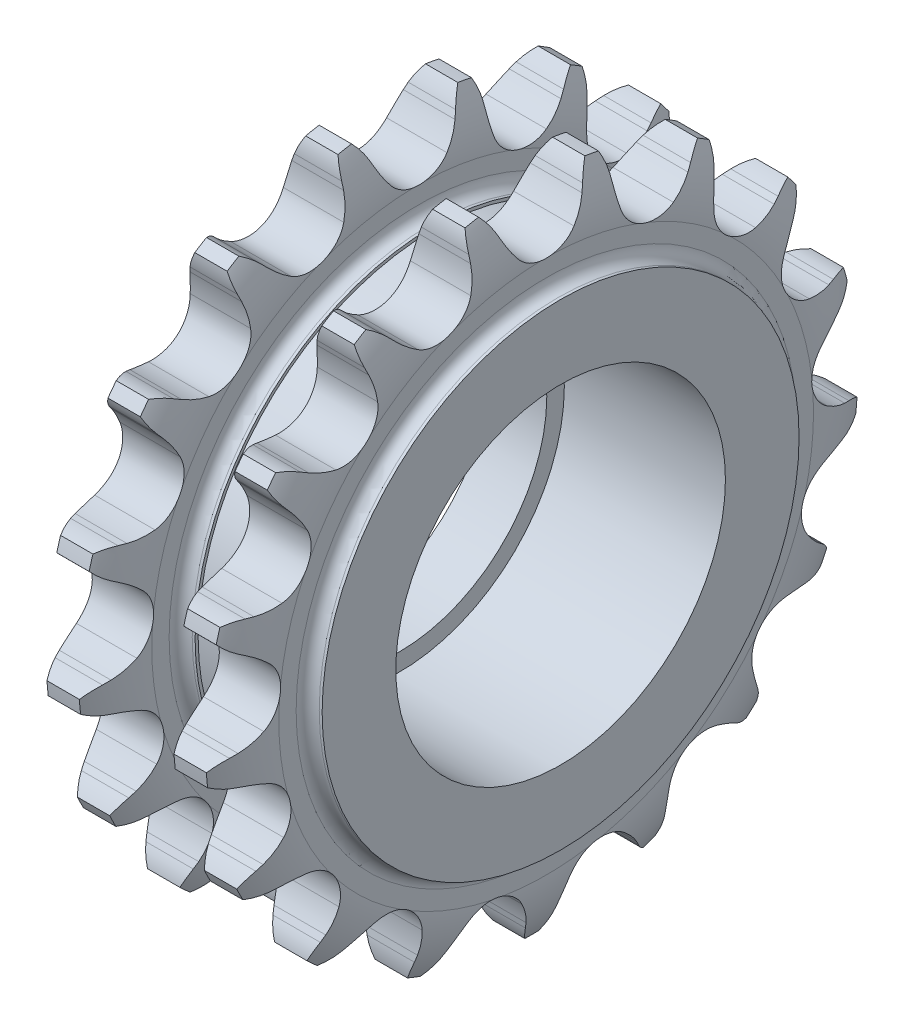
SolidWorks part; units mm, degrees
material "AISI 1020"
ref_plane "Front" through (0, 0, 0) normal (0, 0, 1) x (1, 0, 0)
ref_plane "Top" through (0, 0, 0) normal (0, 1, 0) x (1, 0, 0)
ref_plane "Right" through (0, 0, 0) normal (1, 0, 0) x (0, 0, -1)
sketch "Sketch1" plane through (0, 0, 0) normal (0, 0, 1) x (1, 0, 0)
  line L0 (-4, 0) -> (4, 0) construction
  line L1 (-6.4297, 0) -> (-6.4297, 34)
  line L2 (-6.4297, 34) -> (-6.018, 34)
  line L3 (-4.371, 35.647) -> (-4.371, 38.1174)
  line L4 (-2.3072, 46.5) -> (2.3072, 46.5)
  line L5 (4.371, 38.1174) -> (4.371, 35.647)
  line L6 (6.018, 34) -> (6.4297, 34)
  line L7 (6.4297, 34) -> (6.4297, 0)
  line L8 (6.4297, 0) -> (-6.4297, 0)
  line L9 (0, 0) -> (0, 46.5) construction
  line L10 (-3.7169, 43.1974) -> (3.7169, 43.1974) construction
  line L11 (-3.7169, -43.1974) -> (3.7169, -43.1974) construction
  line L13 (-4.371, 38.1174) -> (3.7984, 38.1174) construction
  line L14 (-4.371, -38.1174) -> (3.7984, -38.1174) construction
  arc A0 (-2.3072, 46.5) -> (-4.371, 38.1174) centre (11.4948, 38.6567) ccw
  arc A1 (2.3072, 46.5) -> (4.371, 38.1174) centre (-11.4948, 38.6567) cw
  arc A2 (4.371, 35.647) -> (6.018, 34) centre (6.018, 35.647) ccw
  arc A3 (-6.018, 34) -> (-4.371, 35.647) centre (-6.018, 35.647) ccw
  point P30 (4.371, 34)
  point P33 (-4.371, 34)
  point P34 (24, 26.331)
  point P36 (34.16, 26.331)
  point P37 (24, 21.8279)
  point P38 (39.09, 21.8279)
  point P39 (24, 17.1531)
  point P40 (33.4, 17.1531)
  point P41 (24, 13.3224)
  point P42 (42.11, 13.3224)
  point P43 (24, 30.8002)
  point P44 (41, 30.8002)
  point P45 (24, 35.1098)
  point P46 (39.875, 35.1098)
  dimension "D1" = 4.1174
  dimension "rx" = 15.875
  dimension "D3" = 1.647
  dimension "d" = 86.3948
  dimension "p" = 15.875
  dimension "z" = 17
  dimension "da" = 93
  dimension "df" = 76.2348
  dimension "dr" = 10.16
  dimension "dg" = 68
  dimension "h" = 15.09
  dimension "bf1" = 8.742
  dimension "b1" = 9.4
  dimension "ba" = 2.0638
  dimension "D2" = 2.0587
  dimension "pt" = 18.11
revolve "Revolve" add sketch "Sketch1" angle 360 about L0
ref_axis "Axis1" through (-8.5448, 0, 0) along (1, 0, 0)
sketch "Sketch2" plane through (0, 0, 0) normal (1, 0, 0) x (0, 0, -1)
  line L0 (0, 0) -> (0, 46.5) construction
  line L1 (0, 0) -> (-8.5444, 45.7082) construction
  line L2 (0, 0) -> (-16.7977, 43.36) construction
  line L3 (4.033, 39.986) -> (5.4737, 38.8388) construction
  line L4 (5.7931, 42.895) -> (-6.3584, 48.2605) construction
  line L5 (0, 0) -> (8.5444, 45.7082) construction
  line L6 (5.7931, 42.895) -> (6.1811, 43.7738)
  line L7 (-5.7931, 42.895) -> (-6.1811, 43.7738)
  circle A0 centre (0, 0) radius 46.5 construction
  arc A1 (4.033, 39.986) -> (-4.033, 39.986) centre (0, 43.1974) cw
  arc A2 (4.033, 39.986) -> (5.7931, 42.895) centre (-6.3584, 48.2605) ccw
  arc A3 (7.5795, 45.8781) -> (6.1811, 43.7738) centre (12.9831, 40.7704) ccw
  arc A4 (-4.033, 39.986) -> (-5.7931, 42.895) centre (6.3584, 48.2605) cw
  arc A5 (-7.5795, 45.8781) -> (-6.1811, 43.7738) centre (-12.9831, 40.7704) cw
  arc A7 (7.5795, 45.8781) -> (-7.5795, 45.8781) centre (0, 0) ccw
  dimension "r1" = 5.1554
  dimension "r3" = 7.4355
  dimension "D1" = 21.176
  dimension "D2" = 10.588
  dimension "av2" = 51.471
  dimension "M" = 6.3584
  dimension "T" = 5.0631
  dimension "beta" = 14.706
  dimension "yv2" = 13.235
  dimension "bc" = 0.9606
extrude "ExtrudeCutOne" cut sketch "Sketch2" against normal mid plane 12.8594
pattern_circular "PatternOne" count 17 over 360 about axis through (-4, 0, 0) along (1, 0, 0) of "ExtrudeCutOne"
pattern_linear "LPatternA" count 2 spacing 18.11 along (1, 0, 0) of bodies 103
sketch "SketchPai" plane through (0, 0, 0) normal (1, 0, 0) x (0, 0, -1)
  circle A0 centre (0, 0) radius 33.565
extrude "Boss-ExtrudeA" add sketch "SketchPai" along normal blind 18.11
sketch "SketchHole" plane through (0, 0, 0) normal (1, 0, 0) x (0, 0, -1)
  circle A0 centre (0, 0) radius 23.5
extrude "Cut-ExtrudeA" cut sketch "SketchHole" against normal through all and the other way through all
sketch "草图4" plane through (-6.4297, 0, 0) normal (-1, 0, 0) x (0, 0, 1)
  circle A0 centre (0, 0) radius 23.5
  circle A1 centre (0, 0) radius 21
  circle A2 centre (0, 0) radius 23.5 construction
  dimension "D1" = 42
extrude "凸台-拉伸2" add sketch "草图4" against normal blind 8
